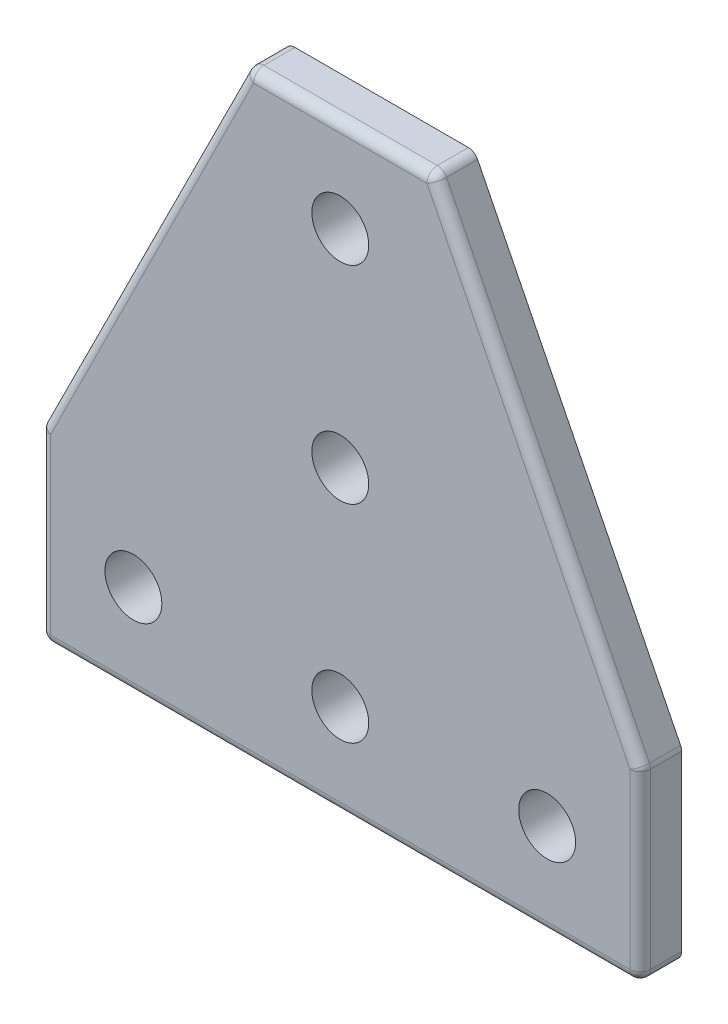
SolidWorks part; units mm, degrees
ref_plane "Front Plane" through (0, 0, 0) normal (0, 0, 1) x (1, 0, 0)
ref_plane "Top Plane" through (0, 0, 0) normal (0, 1, 0) x (1, 0, 0)
ref_plane "Right Plane" through (0, 0, 0) normal (1, 0, 0) x (0, 0, -1)
sketch "Sketch1" plane through (0, 0, 0) normal (0, 0, 1) x (1, 0, 0)
  line L0 (0, 0) -> (0, 18)
  line L1 (9, 9) -> (29, 9) construction
  line L2 (29, 9) -> (49, 9) construction
  line L3 (29, 9) -> (29, 29) construction
  line L4 (38, 58) -> (20, 58)
  line L5 (58, 0) -> (0, 0)
  line L6 (29, 29) -> (29, 49) construction
  line L7 (58, 18) -> (58, 0)
  line L8 (38, 58) -> (58, 18)
  line L9 (58, 9) -> (49, 9) construction
  line L10 (29, 58) -> (29, 49) construction
  line L11 (0, 18) -> (20, 58)
  circle A0 centre (9, 9) radius 2.75
  circle A1 centre (29, 9) radius 2.75
  circle A2 centre (49, 9) radius 2.75
  circle A3 centre (29, 29) radius 2.75
  circle A4 centre (29, 49) radius 2.75
  dimension "D1" = 20
  dimension "E" = 5.5
  dimension "D2" = 9
  dimension "C" = 58
  dimension "D3" = 20
  dimension "B" = 58
  dimension "D4" = 9
  dimension "D5" = 18
extrude "Boss-Extrude1" add sketch "Sketch1" along normal mid plane 4
fillet "Fillet1" radius 1 12 edges at (0, 0, 0) (0, 9, 2) (29, 0, 2) (58, 9, 2) (58, 0, 0) (29, 58, 2) (48, 38, 2) (58, 18, 0) (38, 58, 0) (10, 38, 2) (20, 58, 0) (0, 18, 0)
ref_axis "Axis1" through (29, 49, 2) along (0, 0, -1)
ref_axis "Axis2" through (29, 9, 2) along (0, 0, -1)
ref_axis "Axis3" through (9, 9, 2) along (0, 0, -1)
ref_plane "Plane1" through (29, 0, 0) normal (-1, 0, 0) x (0, 0, 1)
ref_plane "Plane2" through (0, 9, 0) normal (0, 1, 0) x (1, 0, 0)
